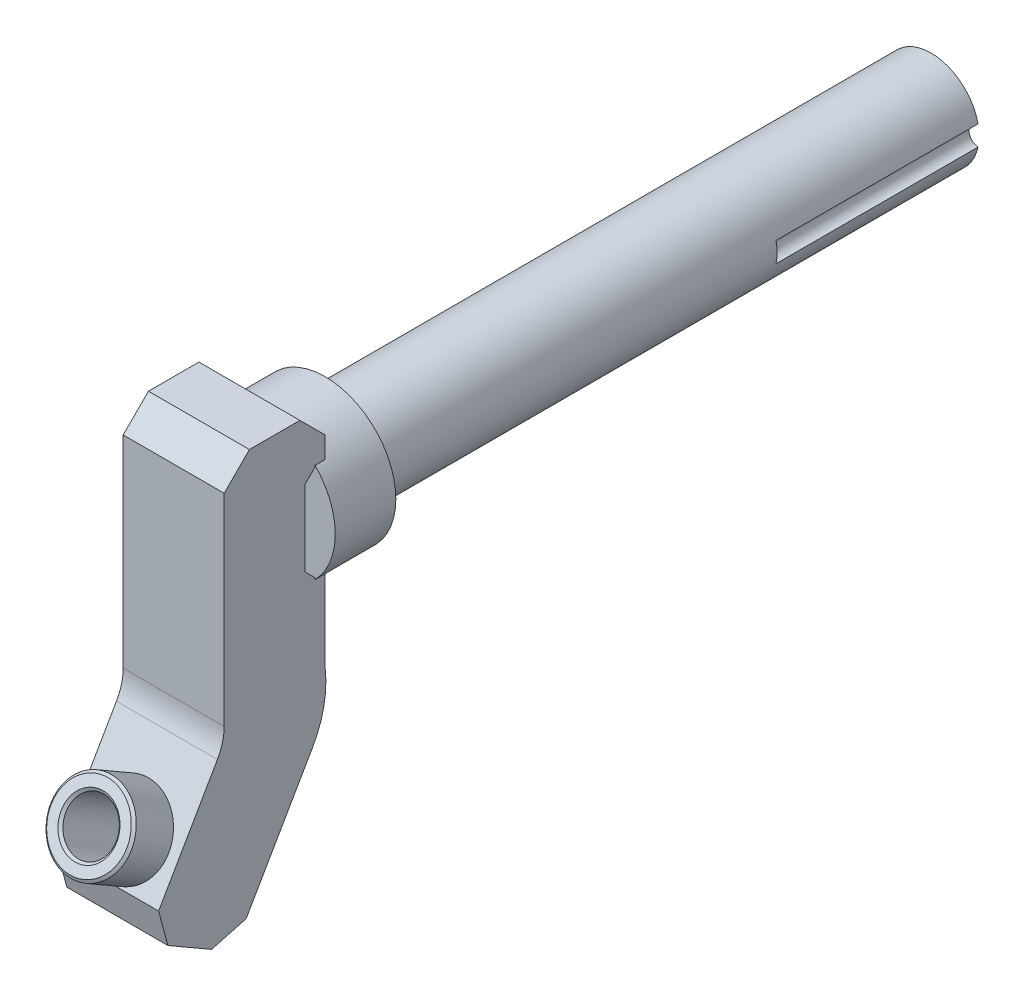
SolidWorks part; units mm, degrees
ref_plane "Piano frontale" through (0, 0, 0) normal (0, 0, 1) x (1, 0, 0)
ref_plane "Piano superiore" through (0, 0, 0) normal (0, 1, 0) x (1, 0, 0)
ref_plane "Piano destro" through (0, 0, 0) normal (1, 0, 0) x (0, 0, -1)
sketch "Schizzo1" plane through (0, 0, 0) normal (0, 0, 1) x (1, 0, 0)
  circle A0 centre (0, 0) radius 9.5
  dimension "D1" = 19
extrude "Estrusione-Estrusione1" add sketch "Schizzo1" along normal blind 120
sketch "Schizzo3" plane through (0, 0, 120) normal (0, 0, 1) x (1, 0, 0)
  circle A0 centre (0, 0) radius 14
  dimension "D1" = 28
extrude "Estrusione-Estrusione2" add sketch "Schizzo3" along normal blind 12
sketch "Schizzo4" plane through (0, 0, 0) normal (1, 0, 0) x (0, 0, -1)
  line L0 (0, 0) -> (-235.6, 0) construction
  line L1 (0, -9.5) -> (0, 9.5) construction
  line L2 (-150, 19) -> (-130, 19)
  line L3 (-150, 19) -> (-150, -26)
  line L6 (-130, 19) -> (-130, 9.5)
  line L7 (-130, 9.5) -> (-134, 9.5)
  line L8 (-134, 9.5) -> (-134, -9.5)
  line L9 (-134, -9.5) -> (-130, -9.5)
  line L10 (-130, -9.5) -> (-130, -26)
  line L11 (-120, 14) -> (-132, 14) construction
  line L12 (-165.4814, -55.4941) -> (-148.1609, -65.4941)
  line L13 (-235.6, 0) -> (-83.0005, -88.1033) construction
  line L14 (-165.4814, -55.4941) -> (-151.3397, -31)
  line L15 (-148.1609, -65.4941) -> (-132.532, -38.4241)
  arc A0 (-151.3397, -31) -> (-150, -26) centre (-160, -26) ccw
  arc A2 (-132.532, -38.4241) -> (-130, -26) centre (-149.8525, -28.4241) ccw
  dimension "D5" = 10
  dimension "D7" = 20
  dimension "D11" = 20
  dimension "D1" = 20
  dimension "D2" = 150
  dimension "D3" = 134
  dimension "D4" = 30
  dimension "D6" = 85.6
  dimension "D8" = 45
  dimension "D9" = 5
  dimension "D10" = 13
extrude "Estrusione-Estrusione5" add sketch "Schizzo4" along normal mid plane 20
sketch "Schizzo5" plane through (0, 57.782, 100.0814) normal (0, 0.5, 0.866) x (1, 0, 0)
  line L1 (0, -102.5167) -> (0, -130.8) construction
  line L2 (10, -102.5167) -> (-10, -102.5167) construction
  line L3 (10, -130.8) -> (-10, -130.8) construction
  circle A0 centre (0, -117.8) radius 8
  dimension "D2" = 16
  dimension "D1" = 13
extrude "Estrusione-Estrusione6" add sketch "Schizzo5" along normal blind 9
sketch "Schizzo6" plane through (0, 62.282, 107.8756) normal (0, 0.5, 0.866) x (1, 0, 0)
  circle A0 centre (0, -117.8) radius 5
  dimension "D1" = 10
extrude "Taglio-Estrusione1" cut sketch "Schizzo6" against normal through all
chamfer "Smusso4" distance 0.5 angle 45 3 edges at (0, -58.5659, 144.1609) (0, -44.0659, 169.2756) (0, -46.664, 170.7756)
chamfer "Smusso5" distance 5 angle 45 4 edges at (0, 19, 130) (0, 19, 150) (0, -65.4941, 148.1609) (0, -55.4941, 165.4814)
chamfer "Smusso6" distance 2 angle 45 2 edges at (0, -9.5, 134) (0, 9.5, 134)
sketch "Schizzo8" plane through (0, 0, 0) normal (0, 0, -1) x (-1, 0, 0)
  line L0 (0, 0) -> (-9.5, 0) construction
  arc A0 (-9.2895, -1.9889) -> (-9.2895, 1.9889) centre (-9.5, 0) ccw
  circle A1 centre (0, 0) radius 9.5 construction
  circle A2 centre (0, 0) radius 9.5 construction
  arc A3 (-9.2895, 1.9889) -> (-9.2895, -1.9889) centre (0, 0) ccw
  dimension "D1" = 7.5
extrude "Taglio-Estrusione2" cut sketch "Schizzo8" against normal blind 40
